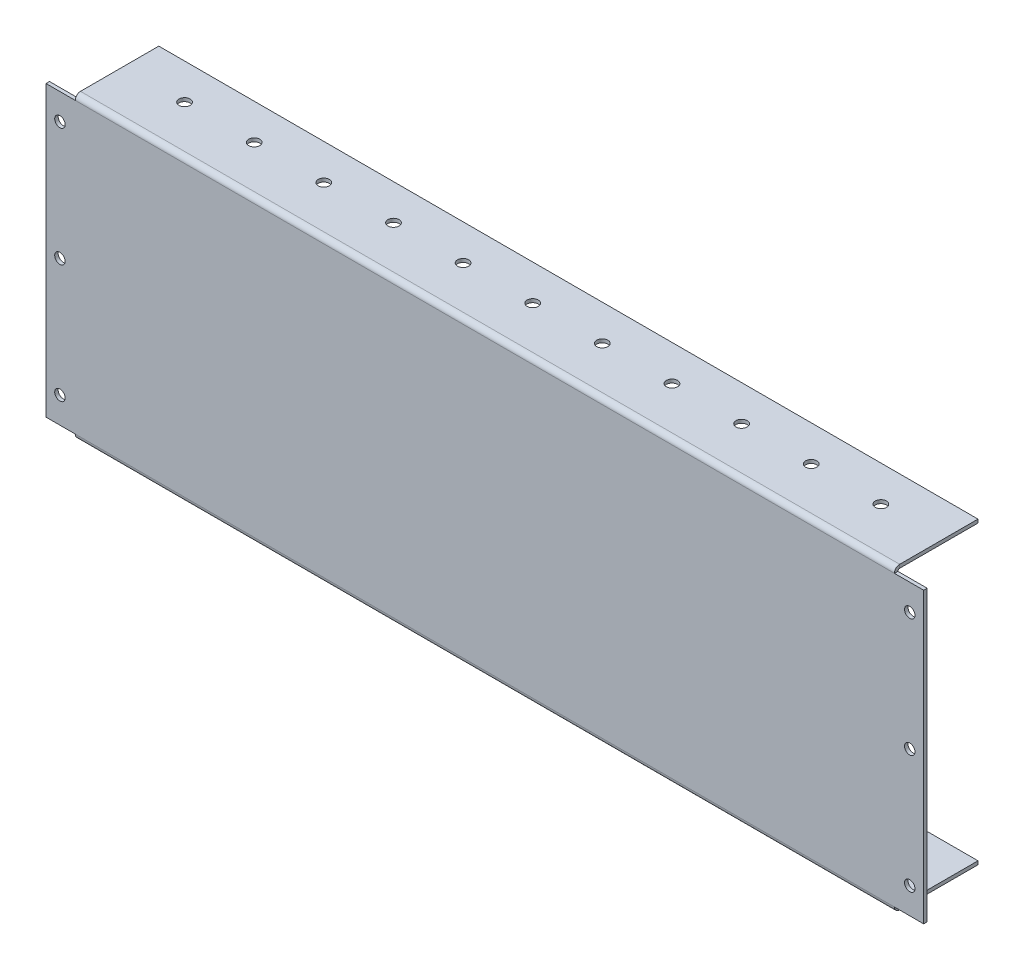
SolidWorks part; units mm, degrees
note: The reader was unsure of these and kept them because the rebuilt part matched: flange length of "Edge-Flange1".
ref_plane "Front Plane" through (0, 0, 0) normal (0, 0, 1) x (1, 0, 0)
ref_plane "Top Plane" through (0, 0, 0) normal (0, 1, 0) x (1, 0, 0)
ref_plane "Right Plane" through (0, 0, 0) normal (1, 0, 0) x (0, 0, -1)
sketch "Model" plane through (0, 0, 0) normal (0, 0, 1) x (1, 0, 0)
  line L0 (-126.05, 42) -> (-126.05, -42)
  line L1 (-126.05, -42) -> (126.05, -42)
  line L2 (126.05, -42) -> (126.05, 42)
  line L3 (126.05, 42) -> (-126.05, 42)
  circle A0 centre (-122.05, 34) radius 1.5
  circle A1 centre (-122.05, -34) radius 1.5
  circle A2 centre (122.05, -34) radius 1.5
  circle A3 centre (122.05, 34) radius 1.5
  circle A4 centre (122.05, 0) radius 1.5
  circle A5 centre (-122.05, 0) radius 1.5
base flange "Base-Flange1" sketch "Model" thickness 1 reverse thickness direction no parameters "D1"=0.7366
edge flange "Edge-Flange1" sketch "Sketch10" flange profiles "Sketch10", "Sketch11" flange angle 90 flange length 24 flange position material outside bend radius 0.5 thickness 1 relief rectangular parameters "D6"=10, "D8"=1
sketch "Sketch10" plane through (0, -42, -1) normal (0, -1, 0) x (-1, 0, 0)
  line L2 (-126.05, 0) -> (-126.05, 23)
  line L3 (-126.05, 23) -> (126.05, 23)
  line L4 (126.05, 23) -> (126.05, 0)
  line L7 (126.05, 0) -> (-126.05, 0) construction
  line L8 (126.05, 0) -> (-126.05, 0)
sketch "Sketch11" plane through (0, 42, -1) normal (0, 1, 0) x (1, 0, 0)
  line L2 (126.05, 0) -> (126.05, 23)
  line L3 (126.05, 23) -> (-126.05, 23)
  line L4 (-126.05, 23) -> (-126.05, 0)
  line L5 (126.05, 0) -> (-126.05, 0) construction
  line L6 (126.05, 0) -> (-126.05, 0)
bend "EdgeBend1" bend radius 0.5 bend angle 90 parameters "D5"=1
bend "EdgeBend2" bend radius 0.5 bend angle 90 parameters "D5"=2
sketch "Sketch13" plane through (0, 43, 0) normal (0, 1, 0) x (1, 0, 0)
  line L0 (0, 1) -> (0, 24) construction
  line L1 (-126.05, 1) -> (126.05, 1) construction
  line L2 (126.05, 24) -> (-126.05, 24) construction
  line L3 (-100, 13.75) -> (-80, 13.75) construction
  line L4 (126.05, 0) -> (-126.05, 0) construction
  circle A0 centre (-100, 13.75) radius 1.6
  circle A1 centre (-80, 13.75) radius 1.6
  circle A2 centre (-60, 13.75) radius 1.6
  circle A3 centre (-40, 13.75) radius 1.6
  circle A4 centre (-20, 13.75) radius 1.6
  circle A5 centre (0, 13.75) radius 1.6
  circle A6 centre (20, 13.75) radius 1.6
  circle A7 centre (40, 13.75) radius 1.6
  circle A8 centre (60, 13.75) radius 1.6
  circle A9 centre (80, 13.75) radius 1.6
  circle A10 centre (100, 13.75) radius 1.6
  dimension "D1" = 3.2
  dimension "D2" = 100
  dimension "D4" = 20
  dimension "D5" = 13.75
  dimension "D3" = 11
extrude "Cut-Extrude1" cut sketch "Sketch13" against normal through all contours A0
sketch "Sketch14" plane through (0, 43, 0) normal (0, 1, 0) x (1, 0, 0)
  line L0 (126.05, 0) -> (-126.05, 0) construction
  line L1 (-126.05, 24) -> (-117.65, 24)
  line L2 (-126.05, 24) -> (-126.05, 0)
  line L3 (-126.05, 0) -> (-117.65, 0)
  line L4 (-117.65, 24) -> (-117.65, 0)
  line L5 (0, 0) -> (0, 51.4246) construction
  line L6 (117.65, 24) -> (117.65, 0)
  line L7 (126.05, 0) -> (117.65, 0)
  line L8 (126.05, 24) -> (126.05, 0)
  line L9 (126.05, 24) -> (117.65, 24)
  dimension "D1" = 8.4
extrude "Cut-Extrude2" cut sketch "Sketch14" against normal blind 1.5 normal cut yes
mirror "Mirror1" about plane through (0, 0, 0) normal (0, 1, 0) of "Cut-Extrude2"
sketch "Bend-Lines1" [suppressed] plane through (0, 0, 0) normal (0, 1, 0) x (1, 0, 0)
sketch "Bounding-Box1" [suppressed] plane through (0, 0, 0) normal (0, 1, 0) x (1, 0, 0)
sheet metal parameters "Sheet-Metal2" thickness 1 parameters "D1"=0.7366
flat pattern "Flat-Pattern2" [suppressed]
sketch "Bend-Lines2" plane through (0, 0, 0) normal (0, 1, 0) x (1, 0, 0)
sketch3d "Bounding-Box2" [suppressed]
  line L0 (126.05, -42, 0) -> (-126.05, -42, 0) construction
  line L1 (126.05, 42, 0) -> (-126.05, 42, 0) construction
  line L2 (126.05, -42, 0) -> (126.05, 42, 0) construction
  line L3 (-126.05, -42, 0) -> (-126.05, 42, 0) construction
sheet metal parameters "Sheet-Metal3" thickness 1 parameters "D1"=0.7366
flat pattern "Flat-Pattern2"
sketch "Bend-Lines2" plane through (0, 0, 0) normal (0, 0, 1) x (1, 0, 0)
  line L0 (126.05, 42.2854) -> (-126.05, 42.2854) construction
  line L1 (-126.05, -42.2854) -> (126.05, -42.2854) construction
  line L2 (126.05, 42.2854) -> (-126.05, 42.2854) construction
  line L3 (-126.05, -42.2854) -> (126.05, -42.2854) construction
sketch3d "Bounding-Box2" [suppressed]
  line L0 (-126.05, -65.5708, 0) -> (126.05, -65.5708, 0) construction
  line L1 (-126.05, 65.5708, 0) -> (126.05, 65.5708, 0) construction
  line L2 (-126.05, -65.5708, 0) -> (-126.05, 65.5708, 0) construction
  line L3 (126.05, -65.5708, 0) -> (126.05, 65.5708, 0) construction
bend of the flat pattern "Flatten-<EdgeBend1>1"
bend of the flat pattern "Flatten-<EdgeBend2>1"
sheet metal parameters "Sheet-Metal4" thickness 1 parameters "D1"=0.7366
flat pattern "Flat-Pattern2"
sketch "Bend-Lines2" plane through (0, 0, 0) normal (0, 0, 1) x (1, 0, 0)
  line L0 (126.05, 42.2854) -> (-126.05, 42.2854) construction
  line L1 (-126.05, -42.2854) -> (126.05, -42.2854) construction
  line L2 (126.05, 42.2854) -> (-126.05, 42.2854) construction
  line L3 (-126.05, -42.2854) -> (126.05, -42.2854) construction
sketch3d "Bounding-Box2" [suppressed]
  line L0 (-126.05, -65.5708, 0) -> (126.05, -65.5708, 0) construction
  line L1 (-126.05, 65.5708, 0) -> (126.05, 65.5708, 0) construction
  line L2 (-126.05, -65.5708, 0) -> (-126.05, 65.5708, 0) construction
  line L3 (126.05, -65.5708, 0) -> (126.05, 65.5708, 0) construction
bend of the flat pattern "Flatten-<EdgeBend1>1"
bend of the flat pattern "Flatten-<EdgeBend2>1"
sheet metal parameters "Sheet-Metal5" thickness 1 parameters "D1"=0.7366
flat pattern "Flat-Pattern2"
sketch "Bend-Lines2" plane through (0, 0, 0) normal (0, 0, 1) x (1, 0, 0)
  line L0 (117.65, 42.2854) -> (-117.65, 42.2854) construction
  line L1 (-126.05, -42.2854) -> (126.05, -42.2854) construction
  line L2 (117.65, 42.2854) -> (-117.65, 42.2854) construction
  line L3 (-126.05, -42.2854) -> (126.05, -42.2854) construction
sketch3d "Bounding-Box2" [suppressed]
  line L0 (-126.05, -65.5708, 0) -> (126.05, -65.5708, 0) construction
  line L1 (-126.05, 65.5708, 0) -> (126.05, 65.5708, 0) construction
  line L2 (-126.05, -65.5708, 0) -> (-126.05, 65.5708, 0) construction
  line L3 (126.05, -65.5708, 0) -> (126.05, 65.5708, 0) construction
bend of the flat pattern "Flatten-<EdgeBend1>1"
bend of the flat pattern "Flatten-<EdgeBend2>1"
sheet metal parameters "Sheet-Metal6" thickness 1 parameters "D1"=0.7366
flat pattern "Flat-Pattern2"
sketch "Bend-Lines2" plane through (0, 0, 0) normal (0, 0, 1) x (1, 0, 0)
  line L0 (117.65, 42.2854) -> (-117.65, 42.2854) construction
  line L1 (-117.65, -42.2854) -> (117.65, -42.2854) construction
  line L2 (117.65, 42.2854) -> (-117.65, 42.2854) construction
  line L3 (-117.65, -42.2854) -> (117.65, -42.2854) construction
sketch3d "Bounding-Box2" [suppressed]
  line L0 (-126.05, -65.5708, 0) -> (126.05, -65.5708, 0) construction
  line L1 (-126.05, 65.5708, 0) -> (126.05, 65.5708, 0) construction
  line L2 (-126.05, -65.5708, 0) -> (-126.05, 65.5708, 0) construction
  line L3 (126.05, -65.5708, 0) -> (126.05, 65.5708, 0) construction
bend of the flat pattern "Flatten-<EdgeBend1>1"
bend of the flat pattern "Flatten-<EdgeBend2>1"
